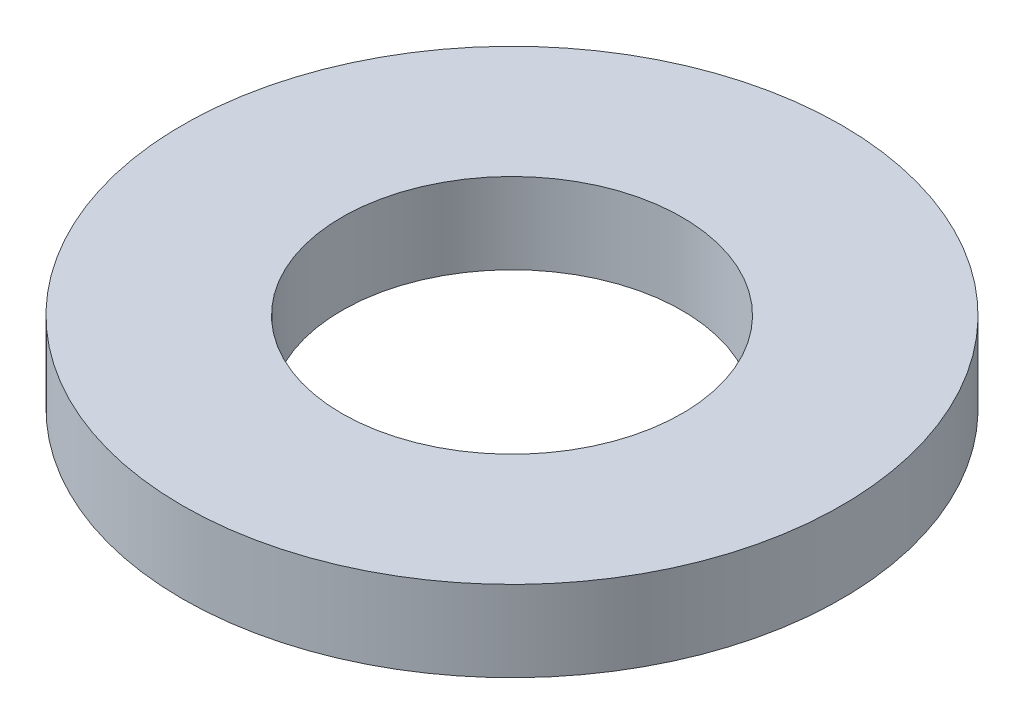
SolidWorks part; units mm, degrees
ref_plane "Front Plane" through (0, 0, 0) normal (0, 0, 1) x (1, 0, 0)
ref_plane "Top Plane" through (0, 0, 0) normal (0, 1, 0) x (1, 0, 0)
ref_plane "Right Plane" through (0, 0, 0) normal (1, 0, 0) x (0, 0, -1)
sketch "Sketch1" plane through (0, 0, 0) normal (0, 1, 0) x (1, 0, 0)
  circle A0 centre (0, 0) radius 77.5
  dimension "FLANGE_OD" = 155
extrude "Boss-Extrude1" add sketch "Sketch1" along normal blind 19
sketch "Sketch2" plane through (0, 0, 0) normal (0, 1, 0) x (1, 0, 0)
  circle A0 centre (0, 0) radius 40
  dimension "BORE_D" = 80
extrude "Cut-Extrude1" cut sketch "Sketch2" along normal through all
sketch "Sketch3" plane through (0, 19, 0) normal (0, 1, 0) x (1, 0, 0)
  circle A0 centre (0, 0) radius 27.5533 construction
  circle A1 centre (-27.5533, 0) radius 3.4934
  dimension "BOLT_D" = 6.9868
  dimension "BOLT_PCD" = 55.1066
extrude "Cut-Extrude2" cut sketch "Sketch3" against normal blind 11.7364 rebuild error yes
pattern_circular "CirPattern1" count 6 over 360 rebuild error yes
